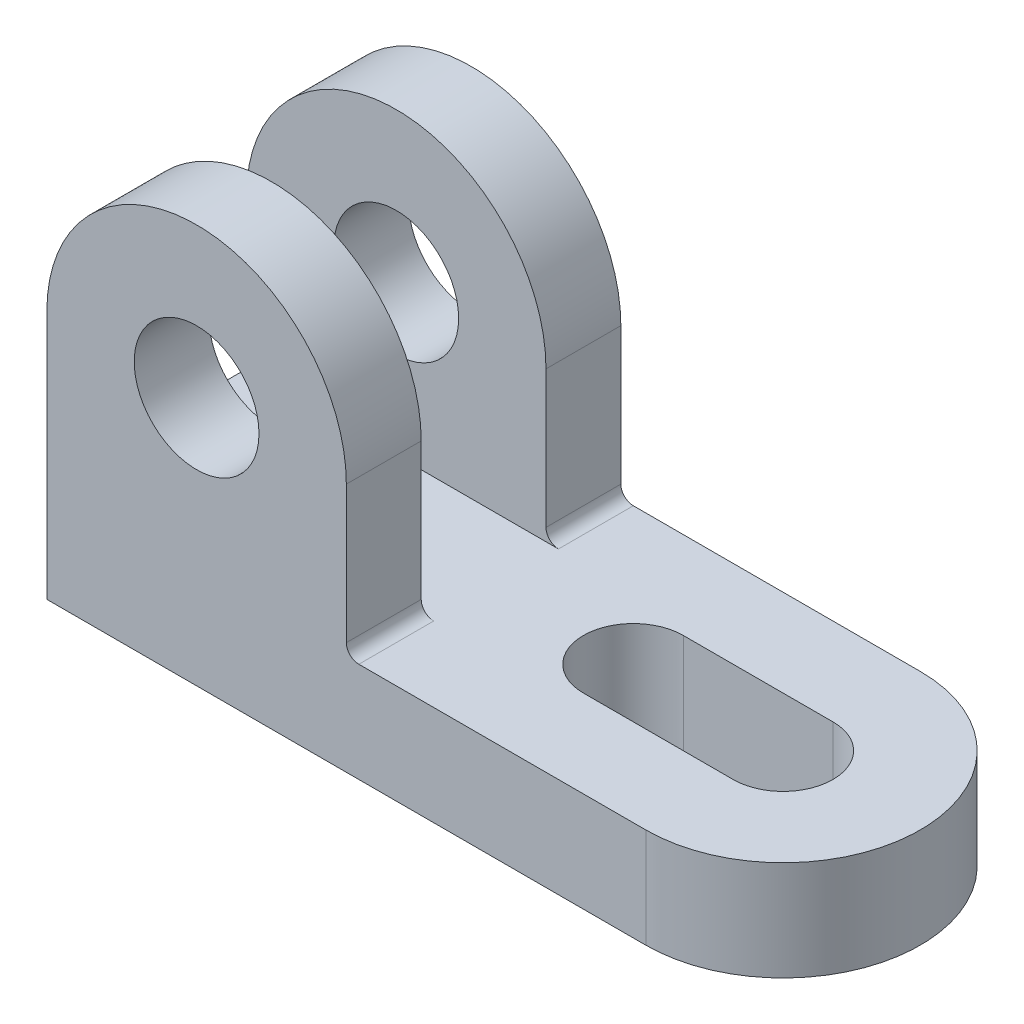
SolidWorks part; units mm, degrees
ref_plane "Front Plane" through (0, 0, 0) normal (0, 0, 1) x (1, 0, 0)
ref_plane "Top Plane" through (0, 0, 0) normal (0, 1, 0) x (1, 0, 0)
ref_plane "Right Plane" through (0, 0, 0) normal (1, 0, 0) x (0, 0, -1)
sketch "Sketch2" plane through (0, 0, 0) normal (0, 1, 0) x (1, 0, 0)
  line L0 (0, -22) -> (0, 22)
  line L1 (0, 22) -> (96, 22)
  line L2 (96, 22) -> (96, -22)
  line L3 (96, -22) -> (0, -22)
  line L4 (96, 22) -> (96, -22)
  line L5 (96, 8) -> (72, 8)
  line L6 (72, 8) -> (72, -8)
  line L7 (72, -8) -> (96, -8)
  arc A0 (96, 22) -> (96, -22) centre (96, 0) cw
  arc A1 (96, 8) -> (96, -8) centre (96, 0) cw
  arc A2 (72, 8) -> (72, -8) centre (72, 0) ccw
  point P4 (0, 0)
  dimension "D1" = 44
  dimension "D2" = 96
  dimension "D3" = 16
  dimension "D4" = 24
extrude "Boss-Extrude1" add sketch "Sketch2" along normal blind 16 contours L3 L2 L1 L0 | A0 L2 region at (43.7493, 0, 0) region at (106.2425, 0, 0)
sketch "Sketch3" plane through (0, 0, 0) normal (0, 0, 1) x (1, 0, 0)
  line L0 (0, 0) -> (0, 40)
  line L1 (0, 40) -> (48, 40)
  line L2 (48, 40) -> (48, 0)
  line L3 (96, 0) -> (0, 0) construction
  line L4 (48, 0) -> (0, 0)
  line L5 (0, 40) -> (48, 40)
  arc A0 (0, 40) -> (48, 40) centre (24, 40) cw
  circle A1 centre (24, 40) radius 10
  dimension "D3" = 20
  dimension "D1" = 40
  dimension "D2" = 48
extrude "Boss-Extrude2" add sketch "Sketch3" along normal blind 12 from offset 10 contours A0 L1 | L4 L2 L1 L0 region at (24, 18.5961, 0) region at (24, 51.4342, 0)
extrude "Boss-Extrude3" add sketch "Sketch3<3>" against normal blind 12 from offset 10 contours A0 L1 | L4 L2 L1 L0 region at (24, 18.5961, 0) region at (24, 51.4342, 0) offset against normal yes
sketch "Sketch3<3>" plane through (0, 0, 0) normal (0, 0, 1) x (1, 0, 0) same geometry as "Sketch3"
fillet "Fillet1" radius 2 2 edges at (48, 16, -16) (48, 16, 16)
